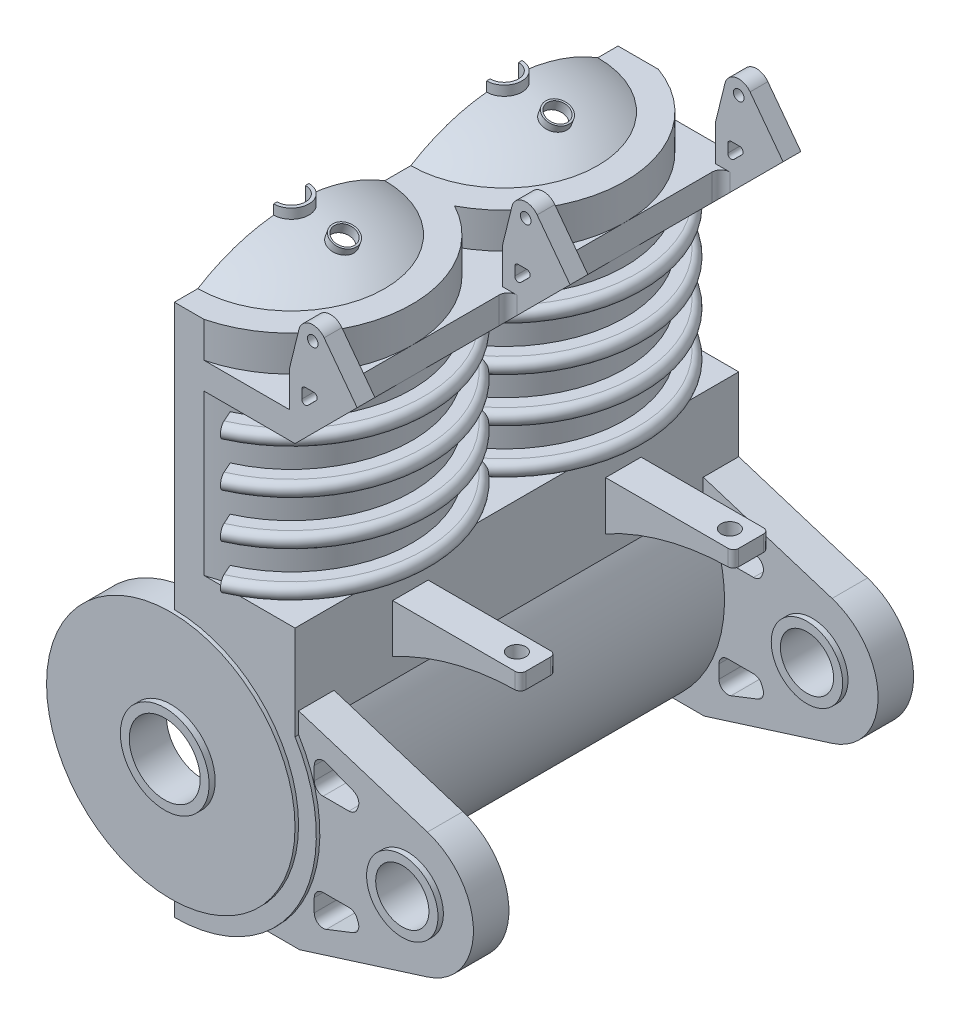
SolidWorks part; units mm, degrees
ref_plane "Front Plane" through (0, 0, 0) normal (0, 0, 1) x (1, 0, 0)
ref_plane "Top Plane" through (0, 0, 0) normal (0, 1, 0) x (1, 0, 0)
ref_plane "Right Plane" through (0, 0, 0) normal (1, 0, 0) x (0, 0, -1)
sketch "Sketch1" plane through (0, 0, 0) normal (0, 0, 1) x (1, 0, 0)
  line L0 (-23.4456, 22.4494) -> (-23.4456, -5.5706)
  line L1 (-16.6456, 6.6436) -> (-16.6456, 22.4494)
  line L2 (-16.6456, 22.4494) -> (-23.4456, 22.4494)
  arc A0 (-23.4456, -5.5706) -> (-16.6456, 6.6436) centre (-23.4456, 2.4294) ccw
  dimension "D1" = 8
  dimension "D2" = 6.8
  dimension "D3" = 28.02
extrude "Boss-Extrude1" add sketch "Sketch1" along normal blind 25
sketch "Sketch2" plane through (0, 22.4494, 0) normal (0, 1, 0) x (1, 0, 0)
  line L0 (-23.4456, -25) -> (-23.4456, 0) construction
  line L1 (-16.6456, -25) -> (-23.4456, -25) construction
  circle A0 centre (-23.4456, -6.41) radius 5
  circle A1 centre (-23.4456, -18.41) radius 5
  dimension "D1" = 12
  dimension "D2" = 10
  dimension "D3" = 6.59
extrude "Cut-Extrude1" cut sketch "Sketch2" against normal blind 20
sketch "Sketch4" plane through (0, 0, 25) normal (0, 0, 1) x (1, 0, 0)
  circle A0 centre (-23.4456, 2.4494) radius 7
  dimension "D1" = 14
extrude "Cut-Extrude2" cut sketch "Sketch4" against normal through all
ref_plane "Plane1" through (0, 20.9494, 0) normal (0, 1, 0) x (1, 0, 0)
sketch "Sketch5" plane through (0, 20.9494, 0) normal (0, 1, 0) x (1, 0, 0)
  line L0 (-23.4456, 0.39) -> (-14.5918, 0.39)
  line L1 (-14.5918, 0.39) -> (-14.5918, -25.21)
  line L2 (-14.5918, -25.21) -> (-23.4456, -25.21)
  arc A9 (-23.4456, -13.21) -> (-23.4456, 0.39) centre (-23.4456, -6.41) ccw
  arc A10 (-20.2456, -12.41) -> (-23.4456, 0.39) centre (-23.4456, -6.41) ccw
  arc A12 (-23.4456, -25.21) -> (-23.4456, -11.61) centre (-23.4456, -18.41) ccw
  arc A13 (-23.4456, -25.21) -> (-20.2456, -12.41) centre (-23.4456, -18.41) ccw
  dimension "D1" = 1.8
  dimension "D2" = 1.8
extrude "Cut-Extrude3" cut sketch "Sketch5" against normal blind 9
sketch "Sketch6" plane through (-23.4456, 0, 0) normal (-1, 0, 0) x (0, 0, 1)
  line L0 (0, 22.4494) -> (0, 9.4494) construction
  line L1 (0.68, 21.5994) -> (0.175, 21.5994)
  line L2 (0.68, 21.5994) -> (0.68, 11.5994)
  line L3 (0.68, 11.5994) -> (0.175, 11.5994)
  line L4 (0.175, 21.5994) -> (0.175, 11.5994)
  line L5 (0.68, 21.5994) -> (0.175, 11.5994) construction
  line L6 (0.68, 11.5994) -> (0.175, 21.5994) construction
  line L7 (1.41, 22.4494) -> (0, 22.4494) construction
  line L9 (0.175, 20.2994) -> (-1.07, 20.2994)
  line L10 (0.175, 20.2994) -> (0.175, 19.4994)
  line L11 (0.175, 19.4994) -> (-1.07, 19.4994)
  line L13 (0.175, 17.7994) -> (-1.07, 17.7994)
  line L14 (0.175, 17.7994) -> (0.175, 16.9994)
  line L15 (0.175, 16.9994) -> (-1.07, 16.9994)
  line L17 (0.175, 15.2994) -> (-1.07, 15.2994)
  line L18 (0.175, 15.2994) -> (0.175, 14.4994)
  line L19 (0.175, 14.4994) -> (-1.07, 14.4994)
  line L21 (0.175, 12.7994) -> (-1.07, 12.7994)
  line L22 (0.175, 12.7994) -> (0.175, 11.9994)
  line L23 (0.175, 11.9994) -> (-1.07, 11.9994)
  line L25 (6.41, 22.4494) -> (6.41, 24.4828) construction
  line L26 (11.41, 22.4494) -> (1.41, 22.4494) construction
  arc A0 (-1.07, 20.2994) -> (-1.07, 19.4994) centre (-1.07, 19.8994) ccw
  arc A1 (-1.07, 17.7994) -> (-1.07, 16.9994) centre (-1.07, 17.3994) ccw
  arc A2 (-1.07, 15.2994) -> (-1.07, 14.4994) centre (-1.07, 14.8994) ccw
  arc A3 (-1.07, 12.7994) -> (-1.07, 11.9994) centre (-1.07, 12.3994) ccw
  point P0 (0.4275, 16.5994)
  dimension "D1" = 0.505
  dimension "D2" = 0.68
  dimension "D3" = 10
  dimension "D4" = 0.85
  dimension "D5" = 0.8
  dimension "D6" = 1.07
  dimension "D7" = 2.5
  dimension "D8" = 2.5
  dimension "D9" = 2.5
  dimension "D10" = 2.15
revolve "Revolve1" add sketch "Sketch6" angle 156 about L25 region at (-23.4456, 16.5994, 0.4275) region at (-23.4456, 19.8994, -0.695) region at (-23.4456, 12.3994, -0.695) region at (-23.4456, 17.3994, -0.695) region at (-23.4456, 14.8994, -0.695) reverse direction yes
pattern_linear "LPattern1" count 2 spacing 12 along (0, 0, 1) of "Revolve1"
sketch "Sketch7" plane through (0, 22.4494, 0) normal (0, 1, 0) x (1, 0, 0)
  circle A0 centre (-23.4456, -6.41) radius 5
extrude "Cut-Extrude4" cut sketch "Sketch7" against normal blind 15
sketch "Sketch8" plane through (0, 0, 0) normal (0, 0, -1) x (-1, 0, 0)
  circle A0 centre (23.4456, 2.4294) radius 7
  circle A1 centre (23.4456, 2.4294) radius 2.5
  dimension "D1" = 5
  dimension "D2" = 14
extrude "Boss-Extrude2" add sketch "Sketch8" along normal blind 0.5 and the other way blind 1
pattern_linear "LPattern2" count 3 spacing 12 along (0, 0, 1) of "Boss-Extrude2"
sketch "Sketch10" plane through (0, 0, 25) normal (0, 0, 1) x (1, 0, 0)
  circle A0 centre (-23.4456, 2.4294) radius 2.5 construction
  circle A1 centre (-23.4456, 2.4294) radius 2.5
  circle A2 centre (-23.4456, 2.4294) radius 7 construction
  circle A3 centre (-23.4456, 2.4294) radius 7
extrude "Boss-Extrude3" add sketch "Sketch10" along normal blind 0.2
sketch "Sketch11" plane through (0, 0, -0.5) normal (0, 0, -1) x (-1, 0, 0)
  circle A0 centre (23.4456, 2.4294) radius 2.5 construction
  circle A1 centre (23.4456, 2.4294) radius 2.5
  circle A2 centre (23.4456, 2.4294) radius 2
  dimension "D1" = 4
extrude "Boss-Extrude4" add sketch "Sketch11" along normal blind 0.5 and the other way blind 1.6
pattern_linear "LPattern3" count 3 spacing 12.22 along (0, 0, 1) of "Boss-Extrude4"
sketch "Sketch13" plane through (0, 22.4494, 0) normal (0, 1, 0) x (1, 0, 0)
  line L1 (-23.4456, -1.41) -> (-23.4456, 0)
  line L2 (-23.4456, 0) -> (-21.1758, 0)
  line L3 (-23.4456, -23.41) -> (-23.4456, -25)
  line L4 (-23.4456, -25) -> (-21.7688, -25)
sketch "Sketch14" plane through (0, 22.4494, 0) normal (0, 1, 0) x (1, 0, 0)
  line L14 (-23.4456, -13.41) -> (-23.4456, -11.41) construction
  line L15 (-23.4456, -23.41) -> (-23.4456, -25) construction
  line L16 (-23.4456, -25) -> (-21.7688, -25) construction
  line L17 (-23.4456, 0) -> (-21.1758, 0) construction
  line L18 (-23.4456, -1.41) -> (-23.4456, 0) construction
  line L19 (-23.4456, -13.41) -> (-23.4456, -11.41)
  line L20 (-23.4456, -23.41) -> (-23.4456, -25)
  line L21 (-23.4456, -25) -> (-21.7688, -25)
  line L22 (-23.4456, 0) -> (-21.1758, 0)
  line L23 (-23.4456, -1.41) -> (-23.4456, 0)
  arc A2 (-23.4456, -23.41) -> (-23.4456, -13.41) centre (-23.4456, -18.41) ccw construction
  arc A3 (-21.7688, -25) -> (-16.6456, -18.41) centre (-23.4456, -18.41) ccw construction
  arc A4 (-16.6456, -18.41) -> (-20.2456, -12.41) centre (-23.4456, -18.41) ccw construction
  arc A5 (-20.2456, -12.41) -> (-16.6456, -6.41) centre (-23.4456, -6.41) ccw construction
  arc A6 (-16.6456, -6.41) -> (-21.1758, 0) centre (-23.4456, -6.41) ccw construction
  arc A7 (-23.4456, -11.41) -> (-23.4456, -1.41) centre (-23.4456, -6.41) ccw construction
  arc A8 (-23.4456, -23.41) -> (-23.4456, -13.41) centre (-23.4456, -18.41) ccw
  arc A9 (-21.7688, -25) -> (-16.6456, -18.41) centre (-23.4456, -18.41) ccw
  arc A10 (-16.6456, -18.41) -> (-20.2456, -12.41) centre (-23.4456, -18.41) ccw
  arc A11 (-20.2456, -12.41) -> (-16.6456, -6.41) centre (-23.4456, -6.41) ccw
  arc A12 (-16.6456, -6.41) -> (-21.1758, 0) centre (-23.4456, -6.41) ccw
  arc A13 (-23.4456, -11.41) -> (-23.4456, -1.41) centre (-23.4456, -6.41) ccw
extrude "Boss-Extrude5" add sketch "Sketch14" along normal blind 2
sketch "Sketch15" plane through (0, 0, 0) normal (0, 0, -1) x (-1, 0, 0)
  line L0 (23.4456, 2.4294) -> (7.4186, 2.4294) construction
  line L1 (10.5016, 1.9869) -> (15.6248, 1.9869) construction
  line L2 (16.6456, 7.8109) -> (9.3869, 5.5223)
  line L3 (16.6456, 6.6436) -> (16.6456, 11.9494) construction
  line L4 (9.3869, -1.5486) -> (16.5912, -3.8201)
  line L5 (16.5912, -3.8201) -> (18.4512, -3.8201)
  line L6 (16.6456, 6.6436) -> (16.6456, 7.8109)
  circle A0 centre (10.5016, 1.9869) radius 2.013
  arc A1 (9.3869, 5.5223) -> (9.3869, -1.5486) centre (10.5016, 1.9869) ccw
  arc A2 (16.6456, 6.6436) -> (23.4456, -5.5706) centre (23.4456, 2.4294) ccw construction
  arc A3 (16.6456, 6.6436) -> (18.4512, -3.8201) centre (23.4456, 2.4294) ccw
  dimension "D1" = 0.4425
  dimension "D3" = 4.026
  dimension "D4" = 3.707
  dimension "D2" = 12.944
  dimension "D5" = 35
  dimension "D6" = 1.86
extrude "Boss-Extrude6" add sketch "Sketch15" against normal blind 2
pattern_linear "LPattern4" count 2 spacing 22.8 along (0, 0, 1) of "Boss-Extrude6"
sketch "Sketch16" plane through (0, 0, 0) normal (0, 0, -1) x (-1, 0, 0)
  circle A0 centre (10.5016, 1.9869) radius 2.013 construction
  circle A1 centre (10.5016, 1.9869) radius 2.013
  circle A2 centre (10.5016, 1.9869) radius 1.5
extrude "Boss-Extrude7" add sketch "Sketch16" along normal blind 0.3 and the other way blind 2.3
pattern_linear "LPattern5" count 2 spacing 22.8 along (0, 0, 1) of "Boss-Extrude7"
sketch "Sketch17" plane through (0, 0, 0) normal (0, 0, -1) x (-1, 0, 0)
  line L0 (13.5691, 5.4529) -> (15.0806, 6.0453)
  line L1 (15.763, 5.5797) -> (15.763, 4.8361)
  line L2 (15.263, 4.3361) -> (13.8108, 4.3361)
  line L3 (13.3453, 4.6537) -> (13.286, 4.805)
  line L4 (10.5016, 1.9869) -> (16.101, 1.9869) construction
  line L5 (15.263, -0.3624) -> (13.8108, -0.3624)
  line L6 (15.763, -1.606) -> (15.763, -0.8624)
  line L7 (13.5691, -1.4792) -> (15.0806, -2.0716)
  line L8 (13.3453, -0.6799) -> (13.286, -0.8312)
  arc A0 (13.5691, 5.4529) -> (13.286, 4.805) centre (13.7515, 4.9874) ccw
  arc A1 (13.8108, 4.3361) -> (13.3453, 4.6537) centre (13.8108, 4.8361) cw
  arc A2 (15.763, 4.8361) -> (15.263, 4.3361) centre (15.263, 4.8361) cw
  arc A3 (15.0806, 6.0453) -> (15.763, 5.5797) centre (15.263, 5.5797) cw
  arc A4 (15.763, -0.8624) -> (15.263, -0.3624) centre (15.263, -0.8624) ccw
  arc A5 (15.0806, -2.0716) -> (15.763, -1.606) centre (15.263, -1.606) ccw
  arc A6 (13.5691, -1.4792) -> (13.286, -0.8312) centre (13.7515, -1.0137) cw
  arc A7 (13.8108, -0.3624) -> (13.3453, -0.6799) centre (13.8108, -0.8624) ccw
  dimension "D1" = 0.5
extrude "Cut-Extrude5" cut sketch "Sketch17" against normal through all
sketch "Sketch18" plane through (-23.4456, 0, 0) normal (-1, 0, 0) x (0, 0, 1)
  line L0 (18.41, 24.4494) -> (18.41, 15.9494) construction
  line L1 (23.41, 24.4494) -> (13.41, 24.4494) construction
  line L2 (11.41, 24.4494) -> (13.41, 24.4494) construction
  line L3 (18.41, 25.9494) -> (18.41, 25.8294)
  line L4 (13.3737, 24.4494) -> (13.1422, 24.4494)
  arc A0 (13.1422, 24.4494) -> (18.41, 25.9494) centre (18.41, 15.9494) cw
  arc A1 (13.3737, 24.4494) -> (18.41, 25.8294) centre (18.41, 15.9494) cw
  arc A2 (13.2054, 24.3474) -> (18.41, 25.8294) centre (18.41, 15.9494) cw construction
  dimension "D1" = 10
  dimension "D2" = 8.5
  dimension "D3" = 0.12
revolve "Revolve2" add sketch "Sketch18" angle 180 about L0
pattern_linear "LPattern6" count 2 spacing 12 along (0, 0, -1) of "Revolve2"
sketch "Sketch19" plane through (0, 24.4494, 0) normal (0, 1, 0) x (1, 0, 0)
  line L0 (-23.4456, -1.1422) -> (-23.4456, -11.6778) construction
  line L1 (-23.4456, -13.1422) -> (-23.4456, -23.6778) construction
  circle A0 centre (-23.4456, -6.41) radius 0.995
  circle A1 centre (-23.4456, -18.41) radius 0.995
  dimension "D1" = 1.99
  dimension "D2" = 1.99
extrude "Cut-Extrude6" cut sketch "Sketch19" along normal blind 10
sketch "Sketch20" plane through (0, 24.4494, 0) normal (0, 1, 0) x (1, 0, 0)
  line L0 (-23.4456, -17.415) -> (-23.4456, -17.61)
  line L1 (-23.4456, -19.21) -> (-23.4456, -19.405)
  line L2 (-23.4456, -5.415) -> (-23.4456, -5.61)
  line L3 (-23.4456, -7.21) -> (-23.4456, -7.405)
  arc A0 (-23.4456, -7.405) -> (-23.4456, -5.415) centre (-23.4456, -6.41) ccw construction
  arc A1 (-23.4456, -7.405) -> (-23.4456, -5.415) centre (-23.4456, -6.41) ccw
  arc A2 (-23.4456, -19.405) -> (-23.4456, -17.415) centre (-23.4456, -18.41) ccw construction
  arc A3 (-23.4456, -19.405) -> (-23.4456, -17.415) centre (-23.4456, -18.41) ccw
  arc A4 (-23.4456, -19.21) -> (-23.4456, -17.61) centre (-23.4456, -18.41) ccw
  arc A5 (-23.4456, -7.21) -> (-23.4456, -5.61) centre (-23.4456, -6.41) ccw
  dimension "D1" = 0.8
  dimension "D2" = 0.8
extrude "Boss-Extrude8" add sketch "Sketch20" along normal blind 0.8 from offset 1.2
ref_plane "Plane2" through (5.1153, 14.054, 0) normal (0.342, 0.9397, 0) x (0, 0, 1)
sketch "Sketch21" plane through (5.1153, 14.054, 0) normal (0.342, 0.9397, 0) x (0, 0, 1)
  line L0 (6.41, -28.0779) -> (6.41, -31.0779) construction
  line L1 (18.41, -28.0779) -> (18.41, -31.0779) construction
  circle A0 centre (6.41, -28.0779) radius 0.6
  circle A1 centre (18.41, -28.0779) radius 0.6
  point P4 (0, 0)
  point P7 (18.41, -28.1194)
  dimension "D1" = 1.2
  dimension "D2" = 1.2
  dimension "D3" = 3
  dimension "D4" = 3
extrude "Cut-Extrude7" cut sketch "Sketch21" along normal through all
sketch "Sketch22" plane through (0, 0, 0) normal (0, 0, -1) x (-1, 0, 0)
  line L0 (16.6456, 20.9494) -> (16.9606, 20.9494)
  line L1 (16.6456, 20.9494) -> (21.1758, 20.9494) construction
  line L2 (16.9606, 20.9494) -> (16.9606, 24.4494)
  line L3 (21.1758, 24.4494) -> (16.6456, 24.4494) construction
  line L4 (16.9606, 24.4494) -> (14.6456, 24.4494)
  line L5 (14.6456, 24.4494) -> (13.5213, 25.5737)
  line L7 (12.7713, 24.8237) -> (16.6456, 20.9494)
  line L8 (15.4547, 23.6402) -> (15.9226, 23.1724)
  line L9 (16.264, 23.3138) -> (16.264, 23.7817)
  line L10 (16.064, 23.9817) -> (15.5962, 23.9817)
  arc A0 (13.5213, 25.5737) -> (12.7713, 24.8237) centre (13.1463, 25.1987) ccw
  arc A1 (13.5213, 25.5737) -> (12.7713, 24.8237) centre (13.1463, 25.1987) ccw
  circle A2 centre (13.1463, 25.1987) radius 0.3
  arc A3 (15.9226, 23.1724) -> (16.264, 23.3138) centre (16.064, 23.3138) ccw
  arc A4 (15.4547, 23.6402) -> (15.5962, 23.9817) centre (15.5962, 23.7817) cw
  arc A5 (16.264, 23.7817) -> (16.064, 23.9817) centre (16.064, 23.7817) ccw
  point P15 (16.264, 23.9817)
  dimension "D5" = 0.6
  dimension "D6" = 1.0607
  dimension "D7" = 0.2
  dimension "D1" = 0.315
  dimension "D2" = 2.315
  dimension "D3" = 1.59
  dimension "D4" = 135
extrude "Boss-Extrude9" add sketch "Sketch22" against normal blind 1 contours L5 A0 L7 L10 L9 L2 L4 A5 A3 L8 A4 A2 region at (-15.3144, 23.4479, 0)
pattern_linear "LPattern7" count 3 spacing 12 along (0, 0, 1) of "Boss-Extrude9"
fillet "Fillet1" radius 0.5 4 edges at (-16.6456, 21.6994, 1) (-16.6456, 21.6994, 13) (-16.6456, 21.6994, 24) (-16.6456, 21.6994, 12)
sketch "Sketch23" plane through (0, 0, 0) normal (0, 0, -1) x (-1, 0, 0)
  line L0 (16.6456, 10.5394) -> (9.4456, 10.5394)
  line L1 (16.6456, 7.8109) -> (16.6456, 11.9494) construction
  line L2 (9.4456, 10.5394) -> (9.4456, 9.6394)
  line L3 (16.6456, 7.7984) -> (16.6456, 10.5394)
  arc A0 (9.4456, 9.6394) -> (16.6456, 7.7984) centre (9.4456, -5.3606) cw
  dimension "D1" = 7.2
  dimension "D3" = 15
  dimension "D2" = 0.9
  dimension "D4" = 8.1
extrude "Boss-Extrude10" add sketch "Sketch23" against normal blind 2 from offset 5.5 offset against normal yes
pattern_linear "LPattern8" count 2 spacing 12 along (0, 0, 1) of "Boss-Extrude10"
sketch "Sketch24" plane through (0, 10.5394, 0) normal (0, 1, 0) x (1, 0, 0)
  line L0 (-10.6456, -6.5) -> (-9.4456, -6.5) construction
  line L1 (-9.4456, -7.5) -> (-9.4456, -5.5) construction
  line L2 (-10.6456, -18.5) -> (-9.4456, -18.5) construction
  line L3 (-9.4456, -19.5) -> (-9.4456, -17.5) construction
  circle A0 centre (-10.6456, -6.5) radius 0.5
  circle A1 centre (-10.6456, -18.5) radius 0.5
  dimension "D1" = 1.2
  dimension "D3" = 1
  dimension "D2" = 1.2
extrude "Cut-Extrude8" cut sketch "Sketch24" against normal blind 2
fillet "Fillet2" radius 0.3 4 edges at (-9.4456, 10.0894, 5.5) (-9.4456, 10.0894, 7.5) (-9.4456, 10.0894, 17.5) (-9.4456, 10.0894, 19.5)
sketch "Sketch25" plane through (0, 0, 0) normal (0, 0, -1) x (-1, 0, 0)
  line L0 (16.9606, 24.4494) -> (14.6456, 24.4494) construction
  line L1 (10.3453, 27.9536) -> (15.0766, 27.9536)
  line L2 (10.3453, 27.9536) -> (10.3453, 24.4494)
  line L3 (10.3453, 24.4494) -> (15.0766, 24.4494)
  line L4 (15.0766, 27.9536) -> (15.0766, 24.4494)
  line L5 (10.3453, 27.9536) -> (15.0766, 24.4494) construction
  line L6 (10.3453, 24.4494) -> (15.0766, 27.9536) construction
  point P0 (12.7109, 26.2015)
extrude "Cut-Extrude9" cut sketch "Sketch25" against normal through all
sketch "Sketch26" plane through (0, 0, 0) normal (0, 0, -1) x (-1, 0, 0)
  line L0 (13.1456, 24.4494) -> (15.0056, 26.9294)
  line L1 (16.4225, 26.6402) -> (16.9606, 24.4494)
  line L2 (23.4456, 26.4494) -> (23.4456, 25.8997) construction
  line L3 (16.9606, 24.4494) -> (13.1456, 24.4494) construction
  arc A0 (15.0056, 26.9294) -> (16.4225, 26.6402) centre (15.6456, 26.4494) cw
  circle A1 centre (15.6456, 26.4494) radius 0.3
  point P10 (0, 0)
  point P12 (15.6698, 26.4639)
  line M2 (16.9606, 24.4494) -> (13.1456, 24.4494)
  dimension "D1" = 7.8
  dimension "D3" = 0.8
  dimension "D4" = 0.6
  dimension "D2" = 2
extrude "Boss-Extrude11" add sketch "Sketch26" against normal blind 1 contours A0 L0 L1 A1 M2 region at (-15.3152, 25.5182, 0)
pattern_linear "LPattern9" count 3 spacing 12 along (0, 0, 1) of "Boss-Extrude11"
extrude "Extrude-Thin1" add sketch "Sketch21<2>" along normal blind 0.5 from offset 1.9 thin thin type one direction wall 0.1
sketch "Sketch21<2>" plane through (5.1153, 14.054, 0) normal (0.342, 0.9397, 0) x (0, 0, 1) same geometry as "Sketch21"
